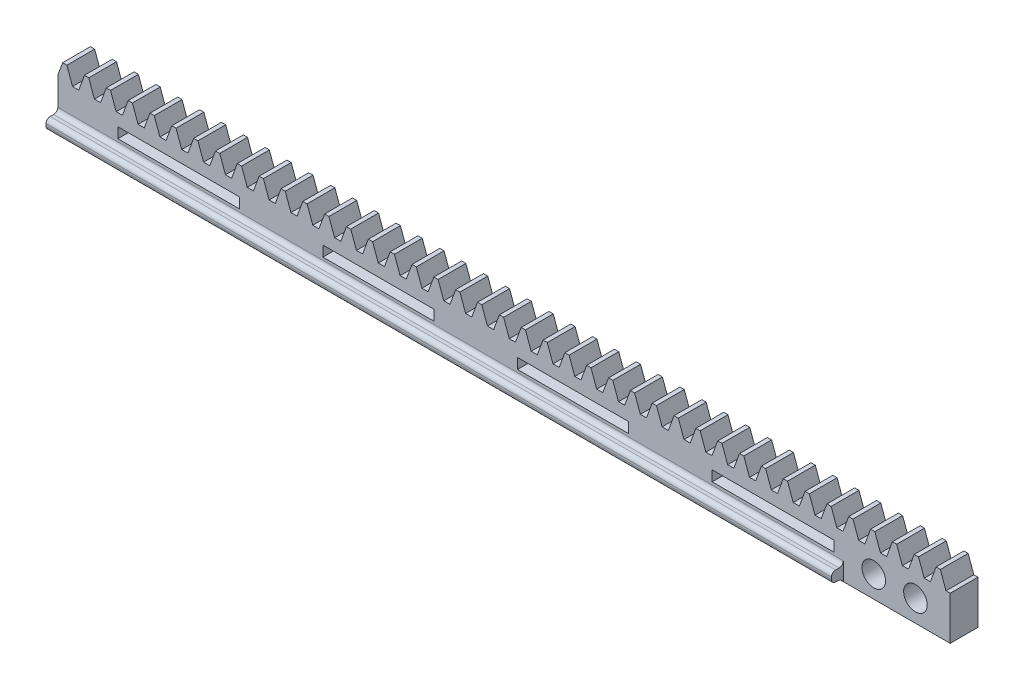
SolidWorks part; units mm, degrees
ref_plane "Plane1" through (0, 0, 0) normal (0, 0, 1) x (1, 0, 0)
ref_plane "Plane2" through (0, 0, 0) normal (0, 1, 0) x (1, 0, 0)
ref_plane "Plane3" through (0, 0, 0) normal (1, 0, 0) x (0, 0, -1)
sketch "HoldingSke" plane through (0, 0, 0) normal (0, 1, 0) x (1, 0, 0)
  line L0 (0, 0) -> (0.1392, 0.9903)
  line L1 (-15, 0) -> (100, 0) construction
  line L2 (0, 0) -> (-2.1039, 2.3779)
  line L3 (0, 0) -> (-11.863, 4.5341)
  line L4 (0, 0) -> (4.1868, 7.5532)
  line L5 (0, 0) -> (-23.7986, -8.8762)
  line L6 (0, 0) -> (-10.5278, -7.1032)
  line L9 (-71.009, 38.7566) -> (103.304, 102.2013)
  line L10 (-76.2, 3.3779) -> (-69.7, 3.3779)
  line L11 (0, 0) -> (-4, 0)
  line L12 (-76.2, 101.6) -> (-76.162, 101.6)
  line L13 (24.9733, 27.94) -> (52.9518, 28.4284)
  line L14 (24.9733, 27.94) -> (24.9743, 27.94)
  line L15 (24.9733, 27.94) -> (100.4006, 29.5858)
  circle A0 centre (0, 0) radius 19.05
  circle A1 centre (0, 0) radius 3.25
  circle A2 centre (0, 0) radius 12.7
  dimension "MPH" = 6.5
  dimension "Diameter" = 38.1
  dimension "Num_teeth" = 61
  dimension "Pitch" = 1
  dimension "Width" = 4
  dimension "Show_teeth" = 998
  dimension "Thickness" = 12.7
  dimension "Ap" = 20
  dimension "Pitch_height" = 6.5
  dimension "Backlash" = 0.038
  dimension "Addendum_fac" = 1
  dimension "Dedendum_fac" = 1.25
  dimension "Clearance_fac" = 0.25
  dimension "Dedendum_add" = 0.001
  dimension "Length" = 185.5
  dimension "Module" = 1
sketch "BlankSke" plane through (0, 0, 0) normal (0, 0, 1) x (1, 0, 0)
  line L1 (0, 0) -> (185.5, 0)
  line L2 (0, 0) -> (0, 7.5)
  line L3 (0, 7.5) -> (185.5, 7.5)
  line L4 (185.5, 0) -> (185.5, 7.5)
  dimension "Length" = 185.5
  dimension "Blank_height" = 7.5
extrude "Blank" add sketch "BlankSke" against normal blind 4
sketch "TooCutSkeIll" plane through (0, 0, 0) normal (0, 0, 1) x (1, 0, 0)
  line L0 (-1.2538, 7.4737) -> (-0.5045, 5.4152)
  line L1 (-0.2687, 5.25) -> (0.2687, 5.25)
  line L2 (0.5045, 5.4152) -> (1.2538, 7.4737)
  line L3 (185.5, 7.5) -> (0, 7.5) construction
  line L4 (0, 0) -> (0, 64.897) construction
  line L5 (-13.208, 6.5) -> (12.954, 6.5) construction
  line L6 (0, 0) -> (185.5, 0) construction
  line L7 (0.8994, 6.5) -> (0.8994, 48.7463) construction
  line L8 (-0.8994, 6.5) -> (-0.8994, 48.7463) construction
  line L9 (1.2914, 7.5) -> (1.2914, 7.5254)
  line L10 (-1.2914, 7.5) -> (-1.2914, 7.5254)
  line L11 (-1.2914, 7.5254) -> (1.2914, 7.5254)
  arc A0 (0.2687, 5.25) -> (0.5045, 5.4152) centre (0.2687, 5.501) ccw
  arc A1 (-0.5045, 5.4152) -> (-0.2687, 5.25) centre (-0.2687, 5.501) ccw
  arc A2 (1.2914, 7.5) -> (1.2538, 7.4737) centre (1.2914, 7.46) ccw
  arc A3 (-1.2538, 7.4737) -> (-1.2914, 7.5) centre (-1.2914, 7.46) ccw
  dimension "Root_fillet" = 0.251
  dimension "Break_rad" = 0.04
  dimension "Pitch_height" = 6.5
  dimension "Gap_width" = 1.7988
  dimension "Dedendum" = 1.25
  dimension "Addendum_plus" = 1.0254
  dimension "Pressure_angle" = 20
extrude "ToothCutIll" [suppressed] cut sketch "TooCutSkeIll" against normal through all
sketch "TooCutSkeSim" plane through (0, 0, 0) normal (0, 0, 1) x (1, 0, 0)
  line L0 (0.4444, 5.25) -> (-0.4444, 5.25)
  line L1 (1.2726, 7.5254) -> (0.4444, 5.25)
  line L2 (0, 17.4625) -> (0, 53.467) construction
  line L3 (1.2726, 7.5254) -> (-1.2726, 7.5254)
  line L6 (-1.2726, 7.5254) -> (-0.4444, 5.25)
  line L9 (-0.8994, 6.5) -> (0.8994, 6.5) construction
  line L10 (0, 0) -> (185.5, 0) construction
  line L11 (0.8994, 6.5) -> (0.8994, 53.467) construction
  line L12 (-0.8994, 6.5) -> (-0.8994, 53.467) construction
  dimension "Pitch_height" = 6.5
  dimension "Pressure_angle" = 20
  dimension "Gap_width" = 1.7988
  dimension "Dedendum" = 1.25
  dimension "Addendum_plus" = 1.0254
extrude "ToothCutSim" cut sketch "TooCutSkeSim" against normal through all
pattern_linear "TeethCuts" count 61 spacing 3.1416 along (1, 0, 0) of "ToothCutIll", "ToothCutSim"
sketch "base-line" plane through (0, 0, 0) normal (0, 0, 1) x (1, 0, 0)
  line L0 (185.5, 2.625) -> (185.5, -2.7625) construction
  line L1 (0, 0) -> (185.5, 0)
  line L2 (0, 0) -> (0, -1)
  line L3 (0, -1) -> (185.5, -1)
  line L4 (185.5, 0) -> (185.5, -1)
  line L5 (185.5, 0) -> (185.5, 5.25) construction
  dimension "D1" = 1
extrude "base" add sketch "base-line" against normal blind 4
sketch "notch-" plane through (0, 0, 0) normal (0, 0, 1) x (1, 0, 0)
  line L0 (0, -1) -> (185.5, -1) construction
  line L3 (18.636, 3.5) -> (121.636, 3.5)
  line L4 (18.636, 3.5) -> (18.636, 2)
  line L5 (18.636, 2) -> (121.636, 2)
  line L6 (121.636, 3.5) -> (121.636, 2)
  dimension "D1" = 1.5
  dimension "D2" = 103
  dimension "D3" = 3
extrude "notch" cut sketch "notch-" against normal through all
sketch "final cut" plane through (0, 0, 0) normal (0, 0, 1) x (1, 0, 0)
  line L1 (138.386, 12.9568) -> (188.0928, 12.9568)
  line L2 (138.386, 12.9568) -> (138.386, -9.2926)
  line L3 (138.386, -9.2926) -> (188.0928, -9.2926)
  line L4 (188.0928, 12.9568) -> (188.0928, -9.2926)
extrude "final-cut" cut sketch "final cut" against normal blind 10
sketch "rail-" plane through (0, 0, 0) normal (0, 0, 1) x (1, 0, 0)
  line L0 (0, -1) -> (138.386, -1) construction
  line L1 (10, 1) -> (123, 1)
  line L2 (10, 1) -> (10, -0.5)
  line L3 (10, -0.5) -> (123, -0.5)
  line L4 (123, 1) -> (123, -0.5)
  line L5 (0, 5.25) -> (0, -1) construction
  dimension "D1" = 0.5
  dimension "D2" = 1.5
  dimension "D3" = 113
  dimension "D4" = 10
extrude "rail" add sketch "rail-" along normal blind 1.7
fillet "Verrundung2" radius 1 1 edges at (66.5, -0.5, 0)
fillet "Verrundung3" radius 0.6 1 edges at (66.5, -0.5, 1.7)
fillet "Verrundung4" radius 0.6 1 edges at (66.5, 1, 0)
fillet "Verrundung5" radius 0.6 1 edges at (66.5, 1, 1.7)
sketch "fillet" plane through (0, 0, 0) normal (0, 0, 1) x (1, 0, 0)
  line L0 (18.636, 2.75) -> (121.636, 2.75) construction
  line L3 (18.636, 3.5) -> (18.636, 2) construction
  line L4 (121.636, 2) -> (121.636, 3.5) construction
  line L5 (70.136, 3.5) -> (70.136, 2) construction
  line L6 (121.636, 3.5) -> (18.636, 3.5) construction
  line L7 (18.636, 2) -> (121.636, 2) construction
  line L9 (64.136, 3.5) -> (76.136, 3.5)
  line L10 (64.136, 3.5) -> (64.136, 2)
  line L11 (64.136, 2) -> (76.136, 2)
  line L12 (76.136, 3.5) -> (76.136, 2)
  line L13 (64.136, 3.5) -> (76.136, 2) construction
  line L14 (64.136, 2) -> (76.136, 3.5) construction
  point P12 (70.136, 2.75)
  dimension "D1" = 12
extrude "filleto" add sketch "fillet" against normal through all
pattern_linear "Lineares Muster1" count 2 spacing 28 along (1, 0, 0) of "filleto"
pattern_linear "Lineares Muster2" count 2 spacing 28 along (-1, 0, 0) of "filleto"
sketch "Skizze2" plane through (0, 0, 0) normal (0, 0, 1) x (1, 0, 0)
  line L1 (10, -1) -> (-6.9989, -1)
  line L2 (10, -1) -> (10, 13.44)
  line L3 (10, 13.44) -> (-6.9989, 13.44)
  line L4 (-6.9989, -1) -> (-6.9989, 13.44)
extrude "Schnitt-Linear austragen1" cut sketch "Skizze2" against normal through all
sketch "Skizze3" plane through (0, 0, 0) normal (0, 0, 1) x (1, 0, 0)
  line L0 (138.386, 2.125) -> (126.2228, 2.125) construction
  line L1 (138.386, 5.25) -> (138.386, -1) construction
  circle A0 centre (127.386, 2.125) radius 1.7
  circle A1 centre (133.386, 2.125) radius 1.7
  dimension "D1" = 3.4
  dimension "D3" = 5
  dimension "D2" = 11
extrude "Schnitt-Linear austragen2" cut sketch "Skizze3" against normal through all
equation "' \"Module@HoldingSke\" = 6.35"
equation "' \"Num_teeth@HoldingSke\" = 12"
equation "' \"Ap@HoldingSke\" =  20"
equation "' \"Width@HoldingSke\" = 0.25 * 25.4"
equation "' \"Show_teeth@HoldingSke\" = 500"
equation "' \"Backlash@HoldingSke\" = 0.009 * 25.4"
equation "' \"Addendum_fac@HoldingSke\" = 1.0"
equation "' \"Dedendum_fac@HoldingSke\" = 1.25"
equation "' \"Dedendum_add@HoldingSke\" = 0.00005 * 25.4"
equation "' \"Clearance_fac@HoldingSke\" = 0.25"
equation "' \"Pitch_height@HoldingSke\" = 1 * 25.4"
equation "' \"Length@HoldingSke\" = 4.71 * 25.4"
equation "\"Pitch@HoldingSke\" = 1 / \"Module@HoldingSke\""
equation "\"MPH@HoldingSke\" = \"Dedendum_fac@HoldingSke\" / \"Pitch@HoldingSke\" + 2 * \"Dedendum_add@HoldingSke\" + 0.002 * 25.4"
equation "\"MPH@HoldingSke\" = ((sgn( \"MPH@HoldingSke\" - \"Pitch_height@HoldingSke\")+1)*( \"MPH@HoldingSke\" - \"Pitch_height@HoldingSke\"))/2 + \"Pitch_height@HoldingSke\""
equation "\"Blank_height@BlankSke\" = \"Pitch_height@HoldingSke\" + \"Addendum_fac@HoldingSke\"  / \"Pitch@HoldingSke\" "
equation "\"Length@BlankSke\" =  \"Length@HoldingSke\""
equation "\"Face_width@Blank\" = \"Width@HoldingSke\""
equation "\"Pressure_angle@TooCutSkeIll\" = \"Ap@HoldingSke\""
equation "\"Addendum_plus@TooCutSkeIll\" =  \"Addendum_fac@HoldingSke\"  / \"Pitch@HoldingSke\" + 0.001 *25.4"
equation "\"Dedendum@TooCutSkeIll\" = \"Dedendum_fac@HoldingSke\"  / \"Pitch@HoldingSke\""
equation "\"Pitch_height@TooCutSkeIll\" =  \"MPH@HoldingSke\""
equation "\"Gap_width@TooCutSkeIll\" = 3.14159265 / 2 / \"Pitch@HoldingSke\" + 6 * \"Backlash@HoldingSke\""
equation "\"Pressure_angle@TooCutSkeSim\" = \"Ap@HoldingSke\""
equation "\"Addendum_plus@TooCutSkeSim\" =  \"Addendum_fac@HoldingSke\"  / \"Pitch@HoldingSke\" + 0.001 * 25.4"
equation "\"Dedendum@TooCutSkeSim\" = \"Dedendum_fac@HoldingSke\"  / \"Pitch@HoldingSke\""
equation "\"Pitch_height@TooCutSkeSim\" =  \"MPH@HoldingSke\""
equation "\"Gap_width@TooCutSkeSim\" = 3.14159265 / 2 / \"Pitch@HoldingSke\" + 6 * \"Backlash@HoldingSke\""
equation "\"Root_fillet@TooCutSkeIll\" = \"Clearance_fac@HoldingSke\" / \"Pitch@HoldingSke\" + \"Dedendum_add@HoldingSke\""
equation "\"Break_rad@TooCutSkeIll\" = 0.02 / \"Pitch@HoldingSke\" * 2"
equation "\"Linear_pitch@TeethCuts\" = 3.14159265 / \"Pitch@HoldingSke\""
equation "\"Num_teeth@HoldingSke\" = int( ( \"Length@HoldingSke\" + 0 ) / (3.14159265 / \"Pitch@HoldingSke\")) + 0.9999  + 1"
equation " \"Num_teeth@TeethCuts\" = int( \"Show_teeth@HoldingSke\" ) + 1"
equation " \"Num_teeth@TeethCuts\" = ((sgn( \"Num_teeth@TeethCuts\" - \"Num_teeth@HoldingSke\" )-1)*( \"Num_teeth@TeethCuts\" - \"Num_teeth@HoldingSke\" ))/-2+ \"Num_teeth@HoldingSke\""
equation " \"Num_teeth@TeethCuts\" = ((sgn( \"Num_teeth@TeethCuts\" - 2.0)+1)*( \"Num_teeth@TeethCuts\" - 2.0))/2 +2.0"
